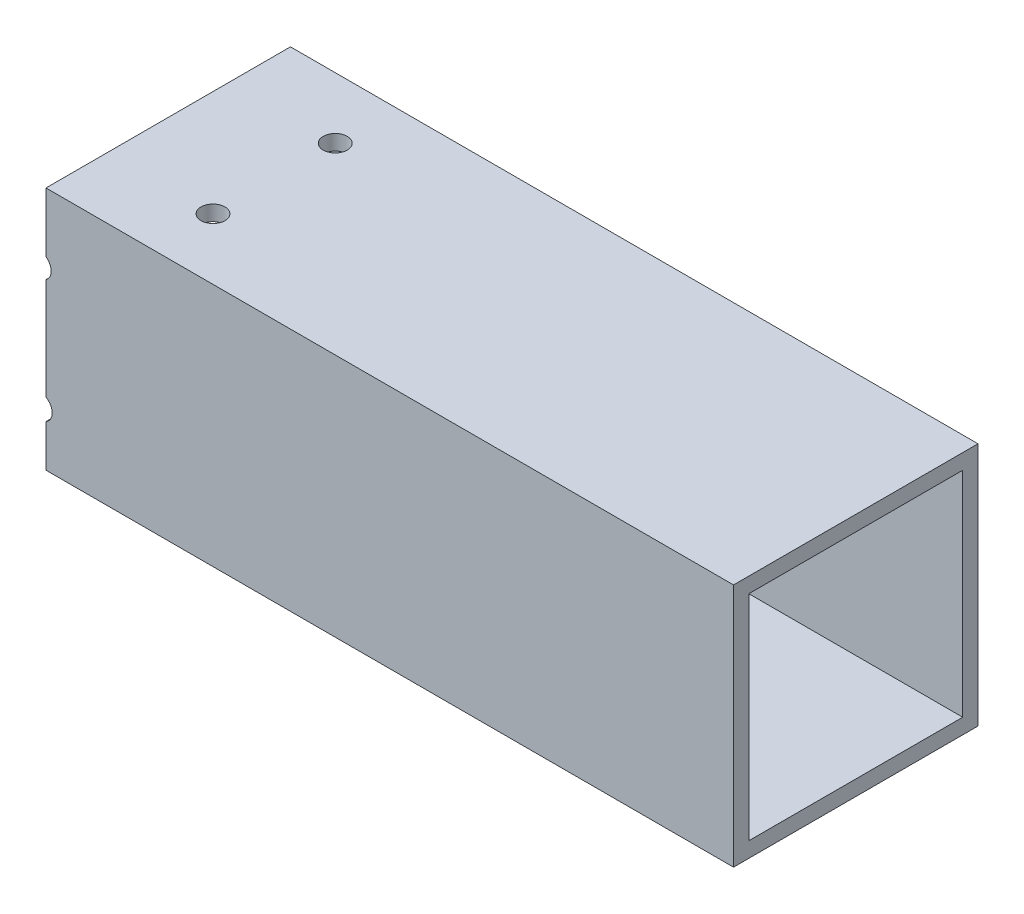
SolidWorks part; units mm, degrees
material "6061-T6 (SS)"
ref_plane "Front Plane" through (0, 0, 0) normal (0, 0, 1) x (1, 0, 0)
ref_plane "Top Plane" through (0, 0, 0) normal (0, 1, 0) x (1, 0, 0)
ref_plane "Right Plane" through (0, 0, 0) normal (1, 0, 0) x (0, 0, -1)
sketch "Sketch1" plane through (0, 0, 0) normal (1, 0, 0) x (0, 0, -1)
  line L1 (0, 0) -> (50.8, 0)
  line L2 (0, 0) -> (0, 50.8)
  line L3 (0, 50.8) -> (50.8, 50.8)
  line L4 (50.8, 0) -> (50.8, 50.8)
  dimension "D1" = 50.8
extrude "Boss-Extrude1" add sketch "Sketch1" along normal blind 142.875
shell "Shell1" thickness 3.175 removed face at (0, 25.4, -25.4) removed face at (142.875, 25.4, -25.4)
sketch "Sketch2" plane through (0, 0, -50.8) normal (0, 0, -1) x (-1, 0, 0)
  circle A0 centre (52.2066, 35.939) radius 2.4892
  circle A1 centre (26.8082, 36.3534) radius 2.4892 construction
  circle A2 centre (52.2074, 36.1462) radius 2.4892 construction
  circle A3 centre (77.6066, 35.939) radius 2.4892 construction
  circle A4 centre (52.2066, 12.7) radius 2.4892
  circle A6 centre (77.3994, 10.5398) radius 2.4892 construction
  circle A7 centre (52.0002, 10.747) radius 2.4892 construction
  circle A8 centre (26.601, 10.9542) radius 2.4892 construction
  circle A10 centre (1.4082, 36.3534) radius 2.4892
  circle A11 centre (26.8082, 36.3534) radius 2.4892
  circle A12 centre (52.2074, 36.1462) radius 2.4892
  circle A13 centre (77.6066, 35.939) radius 2.4892
  circle A14 centre (77.6066, 35.939) radius 2.4892
  circle A15 centre (77.6066, 12.7) radius 2.4892 construction
  circle A16 centre (77.3994, 10.5398) radius 2.4892
  circle A17 centre (52.0002, 10.747) radius 2.4892
  circle A18 centre (26.601, 10.9542) radius 2.4892
  circle A19 centre (1.201, 10.9542) radius 2.4892
  dimension "D3" = 4.9784
  dimension "D1" = 25.4
  dimension "D2" = 25.4
  dimension "D7" = 2
extrude "Cut-Extrude1" cut sketch "Sketch2" against normal through all contours A16 | A13 | A4 | A0 | A18 | A11 | A19 | A10 region at (-52.207, 36.0426, -50.8) region at (-52.3144, 13.7208, -50.8) region at (-1.4082, 36.3534, -50.8) region at (-26.8082, 36.3534, -50.8) region at (-77.6066, 35.939, -50.8) region at (-77.3994, 10.5398, -50.8) region at (-26.601, 10.9542, -50.8) region at (-1.201, 10.9542, -50.8)
sketch "Sketch3" plane through (0, 0, 0) normal (0, -1, 0) x (1, 0, 0)
  line L1 (21.9981, -38.1) -> (21.9981, -12.7) construction
  line L2 (21.9981, -12.7) -> (21.9981, 12.7) construction
  line L3 (180.7481, 0) -> (-416.1519, 0) construction
  line L4 (142.875, -50.8) -> (0, -50.8) construction
  circle A0 centre (21.9981, -12.7) radius 2.4892
  circle A1 centre (21.9981, -38.1) radius 2.4892
  dimension "D1" = 4.9784
  dimension "D2" = 12.7
  dimension "D3" = 12.7
extrude "Cut-Extrude2" cut sketch "Sketch3" against normal through all
pattern_linear "LPattern1" count 6 spacing 25.4 along (-1, 0, 0) of "Cut-Extrude2"
